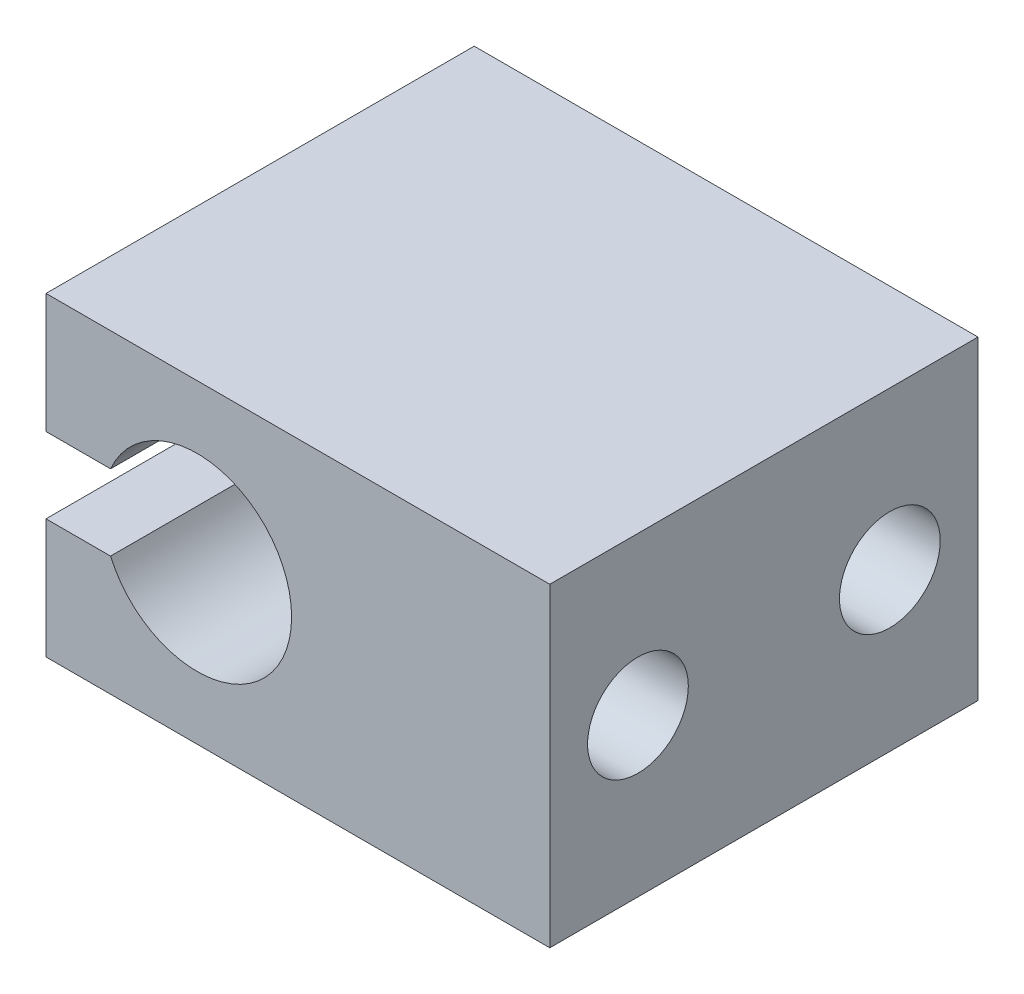
SolidWorks part; units mm, degrees
ref_plane "Front Plane" through (0, 0, 0) normal (0, 0, 1) x (1, 0, 0)
ref_plane "Top Plane" through (0, 0, 0) normal (0, 1, 0) x (1, 0, 0)
ref_plane "Right Plane" through (0, 0, 0) normal (1, 0, 0) x (0, 0, -1)
sketch "Sketch1" plane through (0, 0, 0) normal (0, 0, 1) x (1, 0, 0)
  line L0 (-14.8739, 3) -> (-20, 3)
  line L1 (-20, -12.5) -> (20, -12.5)
  line L2 (-20, -12.5) -> (-20, -3)
  line L3 (-20, 12.5) -> (20, 12.5)
  line L4 (20, -12.5) -> (20, 12.5)
  line L5 (-20, -12.5) -> (20, 12.5) construction
  line L6 (-20, 12.5) -> (20, -12.5) construction
  line L7 (-20, -3) -> (-14.8739, -3)
  line L8 (-20, 3) -> (-20, 12.5)
  arc A0 (-14.8739, -3) -> (-14.8739, 3) centre (-8, 0) ccw
  point P0 (0, 0)
  dimension "D1" = 15
  dimension "D2" = 8
  dimension "D3" = 6
  dimension "D4" = 40
  dimension "D5" = 25
extrude "Boss-Extrude1" add sketch "Sketch1" along normal mid plane 34
sketch "Sketch2" plane through (20, 0, 0) normal (1, 0, 0) x (0, 0, -1)
  circle A0 centre (-10, 0) radius 4
  circle A1 centre (10, 0) radius 4
  dimension "D1" = 8
  dimension "D2" = 10
  dimension "D3" = 10
extrude "Cut-Extrude1" cut sketch "Sketch2" against normal blind 15
